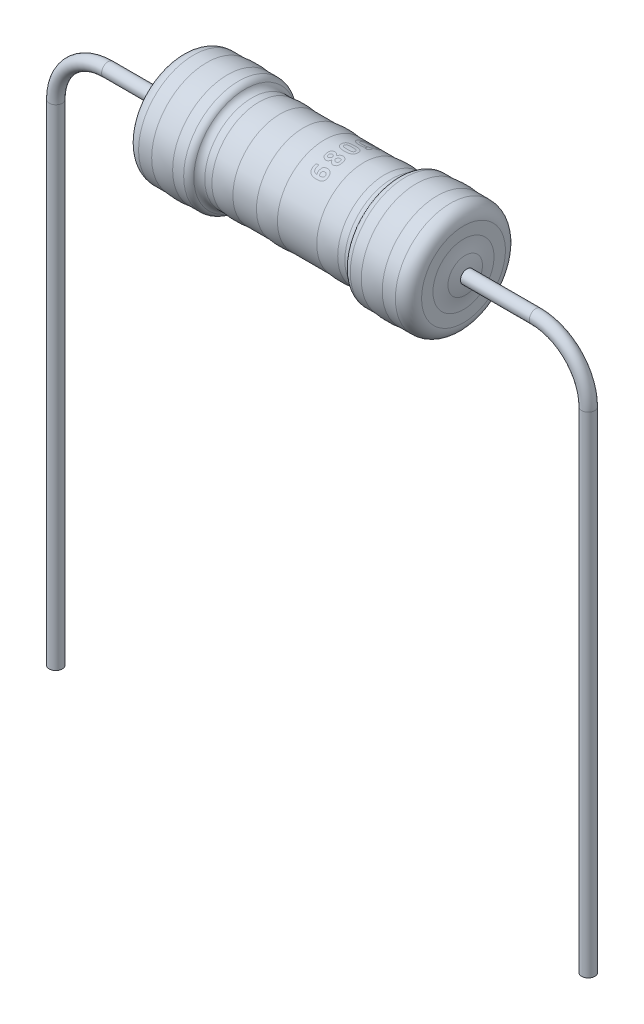
SolidWorks part; units mm, degrees
ref_plane "Front Plane" through (0, 0, 0) normal (0, 0, 1) x (1, 0, 0)
ref_plane "Top Plane" through (0, 0, 0) normal (0, 1, 0) x (1, 0, 0)
ref_plane "Right Plane" through (0, 0, 0) normal (1, 0, 0) x (0, 0, -1)
sketch "Sketch Set Wire Width" plane through (0, 0, 0) normal (0, 0, 1) x (1, 0, 0)
  line L0 (-8.16, 0) -> (8.16, 0)
  line L1 (-10.16, -2) -> (-10.16, -20.6984)
  line L2 (10.16, -2) -> (10.16, -20.6984)
  line L3 (-10.16, -20.6984) -> (10.16, -20.6984) construction
  line L4 (0, 0) -> (0, -20.6984) construction
  arc A0 (-8.16, 0) -> (-10.16, -2) centre (-8.16, -2) ccw
  arc A1 (8.16, 0) -> (10.16, -2) centre (8.16, -2) cw
  dimension "D2" = 2
  dimension "D3" = 60
  dimension "D1" = 20.32
sketch "Sketch Wire Diameter" plane through (0, 0, 0) normal (1, 0, 0) x (0, 0, -1)
  circle A0 centre (0, 0) radius 0.25
  dimension "D1" = 0.5
sweep "SET WIRE LENGTH" add profiles "Sketch Wire Diameter" path "Sketch Set Wire Width"
sketch "Sketch3" plane through (0, 0, 0) normal (0, 0, 1) x (1, 0, 0)
  line L0 (-5.4, 0) -> (5.4, 0)
  line L1 (0, 0) -> (0, 1.8) construction
  line L2 (-2.9, 1.8) -> (2.9, 1.8)
  line L3 (-5.4, 0) -> (-5.4, 1.6)
  line L4 (-4.9, 2.1) -> (-3.18, 2.1)
  line L5 (-2.9, 1.82) -> (-2.9, 1.8)
  line L6 (5.4, 0) -> (5.4, 1.6)
  line L7 (4.9, 2.1) -> (3.18, 2.1)
  line L8 (2.9, 1.82) -> (2.9, 1.8)
  arc A0 (-5.4, 1.6) -> (-4.9, 2.1) centre (-4.9, 1.6) cw
  arc A1 (5.4, 1.6) -> (4.9, 2.1) centre (4.9, 1.6) ccw
  arc A2 (-3.18, 2.1) -> (-2.9, 1.82) centre (-3.18, 1.82) cw
  arc A3 (3.18, 2.1) -> (2.9, 1.82) centre (3.18, 1.82) ccw
  dimension "D5" = 0.5
  dimension "D6" = 0.28
  dimension "D1" = 10.8
  dimension "D2" = 5.8
  dimension "D3" = 1.8
  dimension "D4" = 2.1
revolve "Revolve2" add sketch "Sketch3" angle 360 about L0
fillet "Fillet1" radius 0.3 2 edges at (2.9, 0, 1.8) (-2.9, 0, 1.8)
sketch "Sketch5" plane through (0, 0, 0) normal (0, 0, 1) x (1, 0, 0)
  line L0 (0, 0) -> (2, 0) construction
  line L1 (0, 0) -> (-0.3, 0) construction
  line L2 (-0.3, 0) -> (-2, 0) construction
  line L3 (-2, 0) -> (-4, 0) construction
  line L4 (2, 0) -> (4, 0) construction
  line L5 (-4, 0) -> (-4, 2.1) construction
  line L6 (-0.3, 0) -> (-0.3, 1.8) construction
  line L7 (-2, 0) -> (-2, 1.8) construction
  line L8 (2, 0) -> (2, 1.8) construction
  line L9 (4, 0) -> (4, 2.1) construction
  line L10 (-4, 2.1) -> (-4, 2.13) construction
  line L11 (-4.9, 2.1) -> (-3.18, 2.1) construction
  line L12 (4.9, 2.1) -> (3.18, 2.1) construction
  line L13 (-2.9, 1.8) -> (2.9, 1.8) construction
  line L14 (-2, 1.8) -> (-2, 1.83) construction
  line L17 (-4.4, 2.1) -> (-3.6, 2.1)
  line L19 (-5.4, 0) -> (5.4, 0) construction
  line L22 (-2.4, 1.8) -> (-1.6, 1.8) construction
  line L26 (-0.7, 1.8) -> (0.1, 1.8) construction
  line L30 (1.6, 1.8) -> (2.4, 1.8) construction
  line L34 (3.6, 2.1) -> (4.4, 2.1) construction
  line L36 (-0.3, 1.8) -> (-0.3, 1.83) construction
  line L37 (2, 1.8) -> (2, 1.83) construction
  line L38 (4, 2.1) -> (4, 2.13) construction
  arc A0 (-4.4, 2.1) -> (-3.6, 2.1) centre (-4, -0.5517) cw
  arc A1 (-2.4, 1.8) -> (-1.6, 1.8) centre (-2, -0.8517) cw construction
  arc A2 (-0.7, 1.8) -> (0.1, 1.8) centre (-0.3, -0.8517) cw construction
  arc A3 (1.6, 1.8) -> (2.4, 1.8) centre (2, -0.8517) cw construction
  arc A4 (3.6, 2.1) -> (4.4, 2.1) centre (4, -0.5517) cw construction
  dimension "D3" = 0.8
  dimension "D1" = 4
  dimension "D2" = 4
  dimension "D4" = 0.03
  dimension "D5" = 2
  dimension "D6" = 2
  dimension "D7" = 1.7
revolve "Band 1" add sketch "Sketch5" angle 360 about L2
sketch "Sketch8" plane through (0, 0, 0) normal (0, 0, 1) x (1, 0, 0)
  line L0 (-2.4, 1.8) -> (-1.6, 1.8) construction
  line L1 (-2.4, 1.8) -> (-1.6, 1.8)
  arc A0 (-1.6, 1.8) -> (-2.4, 1.8) centre (-2, -0.8517) ccw construction
  arc A1 (-1.6, 1.8) -> (-2.4, 1.8) centre (-2, -0.8517) ccw
revolve "Band 2" add sketch "Sketch8" angle 360 about L2
sketch "Sketch9" plane through (0, 0, 0) normal (0, 0, 1) x (1, 0, 0)
  line L0 (-0.7, 1.8) -> (0.1, 1.8) construction
  line L1 (-0.7, 1.8) -> (0.1, 1.8)
  arc A0 (0.1, 1.8) -> (-0.7, 1.8) centre (-0.3, -0.8517) ccw construction
  arc A1 (0.1, 1.8) -> (-0.7, 1.8) centre (-0.3, -0.8517) ccw
revolve "Band 3" add sketch "Sketch9" angle 360 about L2
sketch "Sketch10" plane through (0, 0, 0) normal (0, 0, 1) x (1, 0, 0)
  line L0 (1.6, 1.8) -> (2.4, 1.8) construction
  line L1 (1.6, 1.8) -> (2.4, 1.8)
  arc A0 (2.4, 1.8) -> (1.6, 1.8) centre (2, -0.8517) ccw construction
  arc A1 (2.4, 1.8) -> (1.6, 1.8) centre (2, -0.8517) ccw
revolve "Band 4" add sketch "Sketch10" angle 360 about L0
sketch "Sketch11" plane through (0, 0, 0) normal (0, 0, 1) x (1, 0, 0)
  line L0 (3.6, 2.1) -> (4.4, 2.1) construction
  line L1 (3.6, 2.1) -> (4.4, 2.1)
  arc A0 (4.4, 2.1) -> (3.6, 2.1) centre (4, -0.5517) ccw construction
  arc A1 (4.4, 2.1) -> (3.6, 2.1) centre (4, -0.5517) ccw
revolve "Band 5" add sketch "Sketch11" angle 360 about L4
sketch "Sketch12" plane through (0, 0, 0) normal (0, 0, 1) x (1, 0, 0)
  line L0 (-5.35, 0) -> (5.35, 0) construction
  line L1 (-5.35, 1) -> (-5.35, 0)
  line L2 (5.35, 1) -> (5.35, 0)
  line L3 (-5.35, 0) -> (-5.55, 0)
  line L4 (5.35, 0) -> (5.55, 0)
  arc A0 (-5.35, 1) -> (-5.55, 0) centre (-2.95, 0) ccw
  arc A1 (5.35, 1) -> (5.55, 0) centre (2.95, 0) cw
  dimension "D3" = 0.2
  dimension "D4" = 2.6
  dimension "D1" = 10.7
  dimension "D2" = 1
revolve "Revolve10" add sketch "Sketch12" angle 360 about L0
fillet "Fillet2" radius 2 2 edges at (5.4, 0, 0.8703) (-5.4, 0, -0.8703)
ref_plane "Plane2" through (0, 3, 0) normal (0, 1, 0) x (1, 0, 0)
sketch "Sketch13" plane through (0, 3, 0) normal (0, 1, 0) x (1, 0, 0)
  line L0 (0, 0) -> (1.15, 0) construction
  line L1 (1.15, 1.75) -> (1.15, -1.75) construction
  text T0 "680Ω" font "Calibri" height 0.6
  dimension "D1" = 3.5
  dimension "D2" = 1.15
wrap "Wrap1" sketch "Sketch13" wrap type scribe source sketch "Sketch13" face at (0.1, 1.8, 0)
